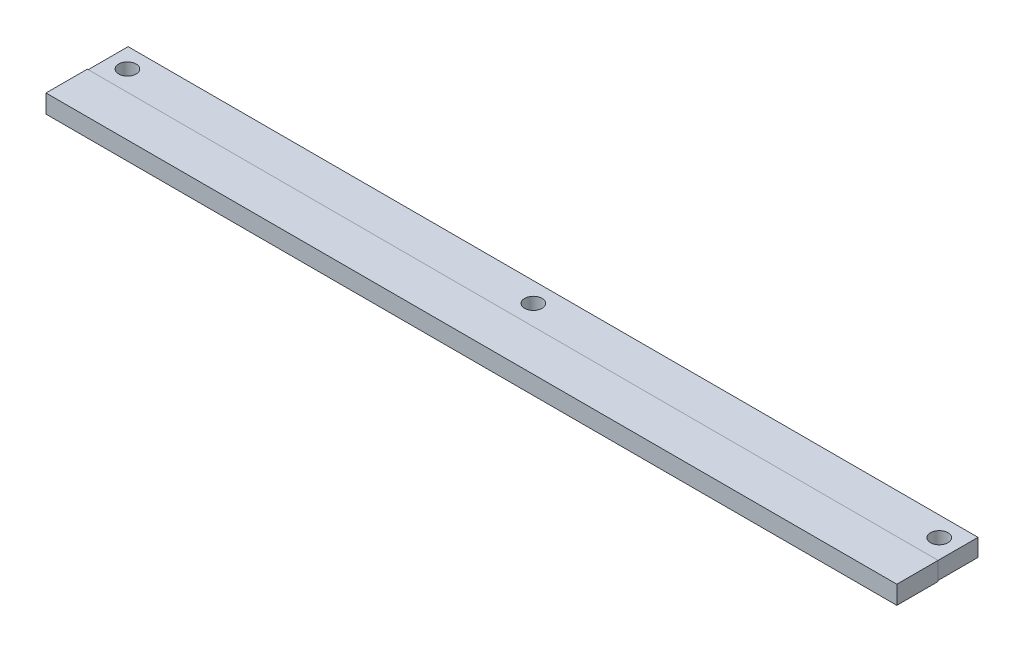
SolidWorks part; units mm, degrees
ref_plane "Front Plane" through (0, 0, 0) normal (1, 0, 0) x (0, 1, 0)
ref_plane "Top Plane" through (0, 0, 0) normal (0, 0, 1) x (0, 1, 0)
ref_plane "Right Plane" through (0, 0, 0) normal (0, 1, 0) x (-1, 0, 0)
sketch "Sketch1" plane through (0, 0, 0) normal (0, 0, 1) x (0, 1, 0)
  line L1 (0, 0) -> (4, 0)
  line L2 (0, 0) -> (0, 185.5)
  line L3 (0, 185.5) -> (4, 185.5)
  line L4 (4, 0) -> (4, 185.5)
  dimension "D1" = 185.5
extrude "Boss-Extrude1" add sketch "Sketch1" along normal blind 18 contours L2 L1 L4 L3
sketch "Sketch2" plane through (0, 4, 0) normal (0, 1, 0) x (-1, 0, 0)
  line L1 (185.5, 0) -> (181.25, 0)
  line L2 (185.5, 0) -> (185.5, 4.5)
  line L3 (185.5, 4.5) -> (181.25, 4.5)
  line L4 (181.25, 0) -> (181.25, 4.5)
  circle A0 centre (181.25, 4.5) radius 1.9
  dimension "D3" = 3.8
  dimension "D1" = 4.25
  dimension "D2" = 4.5
extrude "Cut-Extrude1" cut sketch "Sketch2" against normal up to next contours A0
pattern_linear "LPattern1" count 3 spacing 88.5 along (1, 0, 0) of "Cut-Extrude1"
ref_plane "Plane1" through (0, 0, 9) normal (0, 0, -1) x (-1, 0, 0)
mirror "Mirror1" [suppressed] about plane through (0, 0, 9) normal (0, 0, -1)
sketch "Sketch3" plane through (0, 0, 0) normal (0, 0, -1) x (1, 0, 0)
  line L0 (-185.4, -0.1) -> (-185.4, -3.9)
  line L1 (-185.5, 0) -> (0, 0)
  line L2 (-185.5, 0) -> (-185.5, -4)
  line L3 (-185.5, -4) -> (0, -4)
  line L4 (0, 0) -> (0, -4)
  line L5 (-185.4, -3.9) -> (-0.1, -3.9)
  line L6 (-0.1, -0.1) -> (-0.1, -3.9)
  line L7 (-185.4, -0.1) -> (-0.1, -0.1)
  dimension "D1" = 0.1
extrude "Cut-Extrude2" cut sketch "Sketch3" against normal blind 9
sketch "Sketch5" plane through (0, 3.9, 0) normal (0, 1, 0) x (-1, 0, 0)
  line L0 (0.1, 9) -> (0.1, 0) construction
  line L1 (185.4, 0) -> (0.1, 0)
  line L2 (185.4, 0) -> (185.4, 0.2)
  line L3 (185.4, 0.2) -> (0.1, 0.2)
  line L4 (0.1, 0) -> (0.1, 0.2)
  dimension "D1" = 0.2
extrude "Cut-Extrude3" cut sketch "Sketch5" against normal up to next
equation "\"whitekey_cutout_length\"= 101.5"
equation "\"wall_thickness\"=10"
equation "\"base_mount_height\"=40"
equation "\"base_rear_length\"=80"
equation "\"D1@Sketch1\"=\"base_rear_length\"+\"base_front_length\"-\"dowel_recess_offset\"*2"
equation "\"D2@Sketch1\"=\"wall_thickness\"-\"dowel_recess_offset\"*2"
equation "\"dowel_recess_offset\"=3"
equation "\"guide_brace_height\"=20"
equation "\"guide_brace_thickness\"=2"
equation "\"dowel_recess_depth\"=9"
equation "\"base_front_length\"=111.5"
equation "\"screw_hole_wall_offset\"=7.25"
equation "\"screw_hole_edge_inset\"=4.5"
equation "\"screw_hole_diameter\"=3.8"
equation "\"screw_head_hole_diameter\"=6.7"
equation "\"screw_nut_hole_side_len\"=3.5"
equation "\"D1@Boss-Extrude1\"=\"dowel_recess_depth\"*2"
equation "\"D2@Sketch2\"=\"screw_hole_edge_inset\""
equation "\"D1@Sketch2\"=\"screw_hole_wall_offset\"-\"dowel_recess_offset\""
equation "\"D3@Sketch2\"=\"screw_hole_diameter\""
equation "\"D3@LPattern1\"=0.5*(\"base_front_length\"+\"base_rear_length\"-\"screw_hole_wall_offset\"*2)"
equation "\"D1@Cut-Extrude2\"=\"dowel_recess_depth\""
equation "\"key_mount_recess_length\"=50"
equation "\"key_mount_recess_height\"=12.5"
equation "\"key_mount_recess_depth\"=1.5"
equation "\"screw_shaft_diameter\"=3.5"
equation "\"switch_board_width\"=30"
